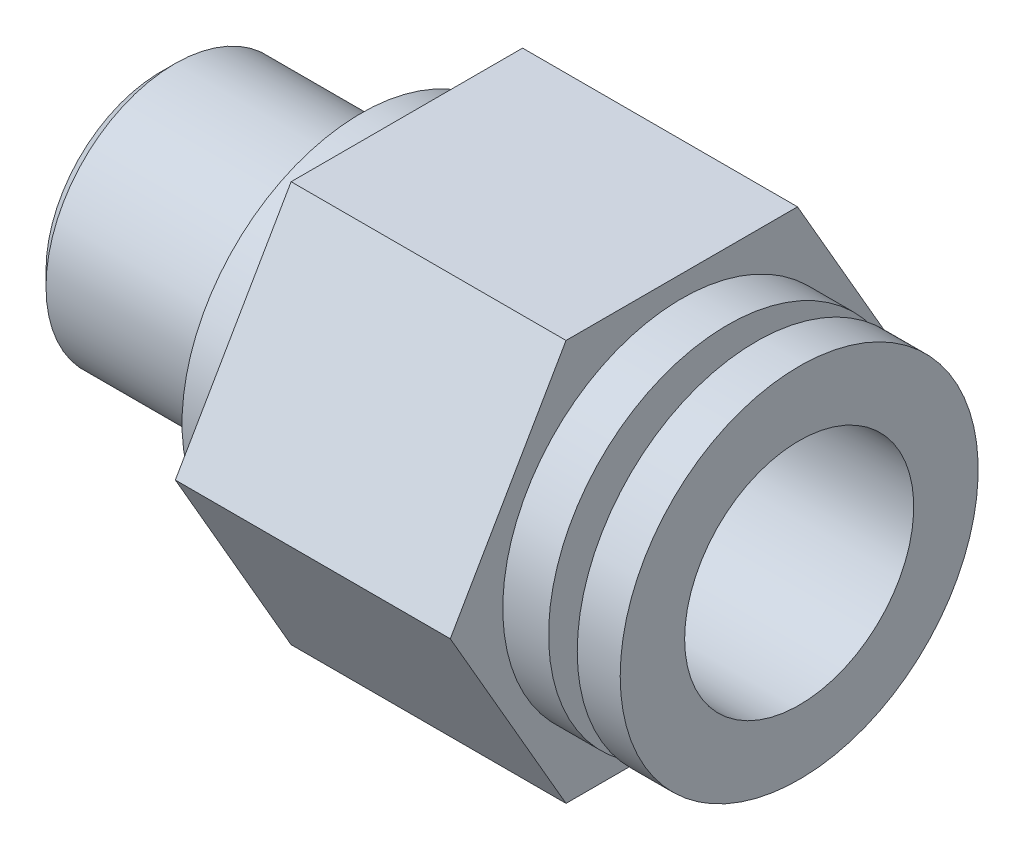
SolidWorks part; units mm, degrees
ref_plane "Front Plane" through (0, 0, 0) normal (0, 0, 1) x (1, 0, 0)
ref_plane "Top Plane" through (0, 0, 0) normal (0, 1, 0) x (1, 0, 0)
ref_plane "Right Plane" through (0, 0, 0) normal (1, 0, 0) x (0, 0, -1)
sketch "Sketch2" plane through (0, 0, 0) normal (1, 0, 0) x (0, 0, -1)
  circle A0 centre (0, 0) radius 9.9219
  dimension "D1" = 19.8438
extrude "Extrude1" add sketch "Sketch2" along normal mid plane 20.32
sketch "Sketch3" plane through (0, 0, 0) normal (1, 0, 0) x (0, 0, -1)
  line L1 (12.8316, 0) -> (6.4158, 11.1125)
  line L2 (6.4158, 11.1125) -> (-6.4158, 11.1125)
  line L3 (-6.4158, 11.1125) -> (-12.8316, 0)
  line L4 (-12.8316, 0) -> (-6.4158, -11.1125)
  line L5 (-6.4158, -11.1125) -> (6.4158, -11.1125)
  line L6 (6.4158, -11.1125) -> (12.8316, 0)
  circle A0 centre (0, 0) radius 11.1125 construction
extrude "Extrude2" add sketch "Sketch3" along normal mid plane 15.24
sketch "Sketch4" plane through (-10.16, 0, 0) normal (-1, 0, 0) x (0, 0, 1)
  circle A0 centre (0, 0) radius 7.1438
  dimension "D1" = 14.2875
extrude "Extrude3" add sketch "Sketch4" along normal blind 11.1125
chamfer "Chamfer1" distance 0.7937 angle 45 1 edges at (-21.2725, 0, 7.1438)
sketch "Sketch5" plane through (0, 0, 0) normal (1, 0, 0) x (0, 0, -1)
  circle A0 centre (0, 0) radius 3.5719
  dimension "D1" = 7.1437
extrude "Cut-Extrude1" cut sketch "Sketch5" against normal through all
sketch "Sketch6" plane through (0, 0, 0) normal (1, 0, 0) x (0, 0, -1)
  circle A0 centre (0, 0) radius 7.1438
  dimension "D1" = 14.2875
extrude "Cut-Extrude2" cut sketch "Sketch6" along normal up to next
sketch "Sketch7" plane through (0, 0, 0) normal (0, 0, 1) x (1, 0, 0)
  line L0 (0, 0) -> (12.2752, 0) construction
  line L1 (0, 7.1437) -> (11.7475, 7.1437)
  line L2 (11.7475, 7.1437) -> (11.7475, 9.9219)
  line L3 (11.7475, 9.9219) -> (14.1288, 9.9219)
  line L4 (14.1288, 9.9219) -> (14.1288, 6.35)
  line L5 (14.1288, 6.35) -> (0, 6.35)
  line L6 (0, 6.35) -> (0, 7.1437)
  line L7 (10.16, -9.9219) -> (10.16, 9.9219) construction
  dimension "D1" = 6.35
  dimension "D2" = 0.7937
  dimension "D3" = 9.9219
  dimension "D4" = 2.3813
  dimension "D5" = 3.9688
revolve "Revolve1" add sketch "Sketch7" angle 360 about L0
other "CPoint1" parameters "Diameter"=12.7, "StubLength"=0
ref_axis "Axis1" through (24.1288, 0, 0) along (-1, 0, 0)
